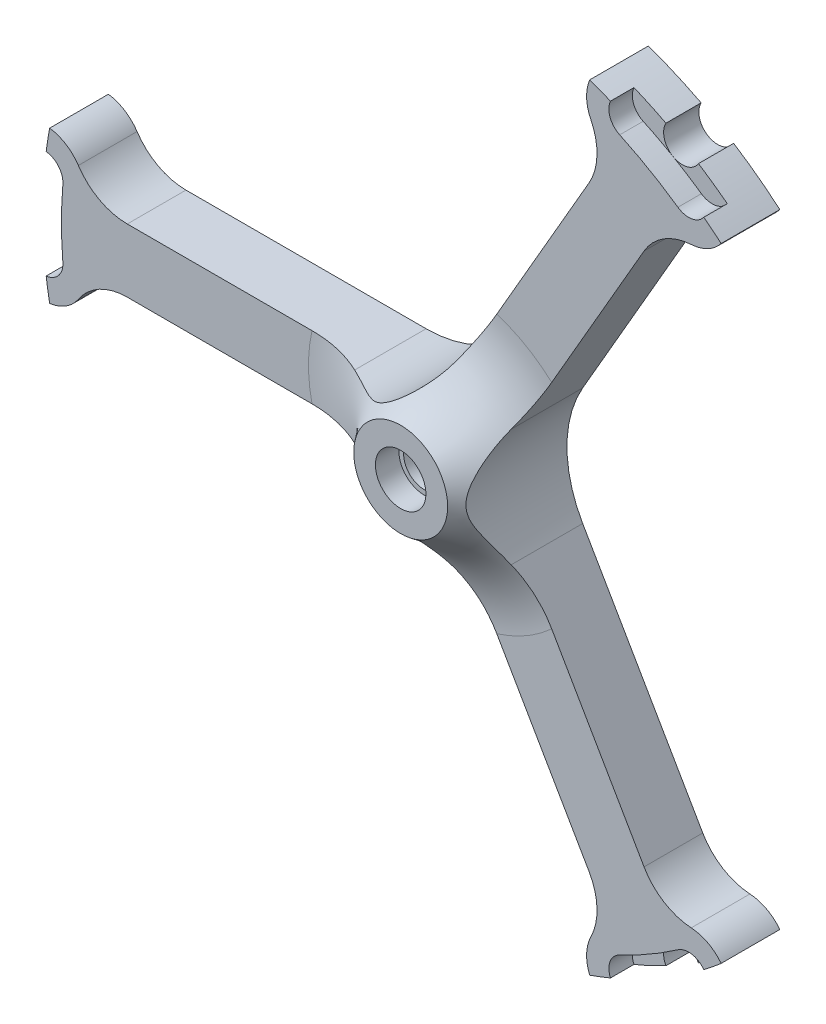
SolidWorks part; units mm, degrees
ref_plane "Plan de face" through (0, 0, 0) normal (0, 0, 1) x (1, 0, 0)
ref_plane "Plan de dessus" through (0, 0, 0) normal (0, 1, 0) x (1, 0, 0)
ref_plane "Plan de droite" through (0, 0, 0) normal (1, 0, 0) x (0, 0, -1)
sketch "Esquisse1" plane through (0, 0, 0) normal (0, 0, 1) x (1, 0, 0)
  line L19 (-1000, 0) -> (49000, 0) construction
  line L21 (-27.7888, 2.7) -> (-7.3323, 2.7)
  line L23 (-27.7888, -2.7) -> (-7.3323, -2.7)
  line L33 (16.2327, 22.7158) -> (6.0044, 5)
  line L34 (11.5561, 25.4158) -> (1.3279, 7.7)
  line L35 (11.5561, -25.4158) -> (1.3279, -7.7)
  line L36 (16.2327, -22.7158) -> (6.0044, -5)
  arc A0 (-34.3972, 6.4678) -> (-34.6976, 4.5906) centre (0, 0) ccw
  arc A7 (-33.2771, 2.8629) -> (-34.6976, 4.5906) centre (-34.8712, 3) ccw
  arc A8 (-33.2771, -2.8629) -> (-34.6976, -4.5906) centre (-34.8712, -3) cw
  arc A12 (-33.2771, 2.8629) -> (-33.2771, -2.8629) centre (0, 0) ccw
  arc A13 (-31.9549, 4.9353) -> (-34.3972, 6.4678) centre (-34.8712, 3) ccw
  arc A14 (-31.9549, -4.9353) -> (-34.3972, -6.4678) centre (-34.8712, -3) cw
  arc A15 (-34.6976, -4.5906) -> (-34.3972, -6.4678) centre (0, 0) ccw
  arc A16 (-27.7888, -2.7) -> (-31.9549, -4.9353) centre (-27.7888, -7.7) ccw
  arc A17 (-27.7888, 2.7) -> (-31.9549, 4.9353) centre (-27.7888, 7.7) cw
  arc A48 (22.7998, 26.555) -> (21.3244, 27.7538) centre (0, 0) ccw
  arc A49 (19.1178, 27.3874) -> (21.3244, 27.7538) centre (20.0337, 28.6993) ccw
  arc A50 (14.1592, 30.2502) -> (13.3733, 32.3443) centre (14.8375, 31.6993) cw
  arc A51 (19.1178, 27.3874) -> (14.1592, 30.2502) centre (0, 0) ccw
  arc A52 (20.2516, 25.2061) -> (22.7998, 26.555) centre (20.0337, 28.6993) ccw
  arc A53 (11.7034, 30.1414) -> (11.5974, 33.0227) centre (14.8375, 31.6993) cw
  arc A54 (13.3733, 32.3443) -> (11.5974, 33.0227) centre (0, 0) ccw
  arc A55 (11.5561, 25.4158) -> (11.7034, 30.1414) centre (7.226, 27.9158) ccw
  arc A56 (16.2327, 22.7158) -> (20.2516, 25.2061) centre (20.5628, 20.2158) cw
  arc A57 (11.5974, -33.0227) -> (13.3733, -32.3443) centre (0, 0) ccw
  arc A58 (14.1592, -30.2502) -> (13.3733, -32.3443) centre (14.8375, -31.6993) ccw
  arc A59 (19.1178, -27.3874) -> (21.3244, -27.7538) centre (20.0337, -28.6993) cw
  arc A60 (14.1592, -30.2502) -> (19.1178, -27.3874) centre (0, 0) ccw
  arc A61 (11.7034, -30.1414) -> (11.5974, -33.0227) centre (14.8375, -31.6993) ccw
  arc A62 (20.2516, -25.2061) -> (22.7998, -26.555) centre (20.0337, -28.6993) cw
  arc A63 (21.3244, -27.7538) -> (22.7998, -26.555) centre (0, 0) ccw
  arc A64 (16.2327, -22.7158) -> (20.2516, -25.2061) centre (20.5628, -20.2158) ccw
  arc A65 (11.5561, -25.4158) -> (11.7034, -30.1414) centre (7.226, -27.9158) cw
  arc A66 (-7.3323, -2.7) -> (1.3279, -7.7) centre (-7.3323, -12.7) cw
  arc A67 (6.0044, -5) -> (6.0044, 5) centre (14.6647, 0) cw
  arc A68 (1.3279, 7.7) -> (-7.3323, 2.7) centre (-7.3323, 12.7) cw
  point P38 (0, 0)
  point P50 (3.1177, 0)
  point P55 (0, 0)
  point P56 (0, 0)
  point P80 (0, 0)
  dimension "D1" = 70
  dimension "D3" = 3
  dimension "D2" = 3.2
  dimension "D4" = 5
  dimension "D5" = 10
extrude "Boss.-Extru.1" add sketch "Esquisse1" along normal blind 5
sketch "Esquisse7" plane through (0, 0, 0) normal (0, 0, -1) x (-1, 0, 0)
  line L0 (-1000, 0) -> (49000, 0) construction
  arc A0 (34.6976, -4.5906) -> (34.6976, 4.5906) centre (0, 0) ccw
  arc A2 (33.2771, -2.8629) -> (33.2771, 2.8629) centre (0, 0) ccw
  arc A4 (34.9634, 1.5996) -> (34.9634, -1.5996) centre (35, 0) ccw
  arc A5 (34.6976, 4.5906) -> (33.2771, 2.8629) centre (34.8712, 3) ccw
  arc A6 (33.2771, -2.8629) -> (33.2771, 2.8629) centre (0, 0) ccw construction
  arc A7 (34.6976, -4.5906) -> (33.2771, -2.8629) centre (34.8712, -3) cw
  arc A8 (-21.3244, -27.7538) -> (-13.3733, -32.3443) centre (0, 0) ccw
  arc A9 (-19.1178, -27.3874) -> (-14.1592, -30.2502) centre (0, 0) ccw
  arc A10 (-16.0964, -31.079) -> (-18.867, -29.4794) centre (-17.5, -30.3109) ccw
  arc A11 (-13.3733, -32.3443) -> (-14.1592, -30.2502) centre (-14.8375, -31.6993) ccw
  arc A12 (-21.3244, -27.7538) -> (-19.1178, -27.3874) centre (-20.0337, -28.6993) cw
  arc A13 (-13.3733, 32.3443) -> (-21.3244, 27.7538) centre (0, 0) ccw
  arc A14 (-14.1592, 30.2502) -> (-19.1178, 27.3874) centre (0, 0) ccw
  arc A15 (-18.867, 29.4794) -> (-16.0964, 31.079) centre (-17.5, 30.3109) ccw
  arc A16 (-21.3244, 27.7538) -> (-19.1178, 27.3874) centre (-20.0337, 28.6993) ccw
  arc A17 (-13.3733, 32.3443) -> (-14.1592, 30.2502) centre (-14.8375, 31.6993) cw
  point P36 (0, 0)
  arc M44 (34.6976, -4.5906) -> (33.2771, -2.8629) centre (34.8712, -3) cw
  arc M45 (33.2771, -2.8629) -> (33.2771, 2.8629) centre (0, 0) ccw
  arc M46 (33.2771, 2.8629) -> (34.6976, 4.5906) centre (34.8712, 3) cw
  arc M56 (-13.3733, 32.3443) -> (-14.1592, 30.2502) centre (-14.8375, 31.6993) cw
  arc M57 (-14.1592, 30.2502) -> (-19.1178, 27.3874) centre (0, 0) ccw
  arc M58 (-19.1178, 27.3874) -> (-21.3244, 27.7538) centre (-20.0337, 28.6993) cw
  arc M68 (-21.3244, -27.7538) -> (-19.1178, -27.3874) centre (-20.0337, -28.6993) cw
  arc M69 (-19.1178, -27.3874) -> (-14.1592, -30.2502) centre (0, 0) ccw
  arc M70 (-14.1592, -30.2502) -> (-13.3733, -32.3443) centre (-14.8375, -31.6993) cw
  dimension "D1" = 3.2
  dimension "D3" = 3.2
  dimension "D4" = 70
  dimension "D2" = 3
extrude "Boss.-Extru.5" add sketch "Esquisse7" against normal blind 3 contours A4 A0 A2 M46 | A4 A0 M45 M44 | A10 A8 A9 M70 | A10 A8 M69 M68 | A15 A13 M57 M56 | A15 A13 A14 M58 region at (-34.0862, -2.7129, 0) region at (-34.0862, 2.7129, 0) region at (19.3926, -28.1631, 0) region at (14.6937, -30.876, 0) region at (14.6937, 30.876, 0) region at (19.3926, 28.1631, 0)
sketch "Esquisse4" plane through (0, 0, 5) normal (0, 0, 1) x (1, 0, 0)
  circle A1 centre (0, 0) radius 4
  dimension "D1" = 8
extrude "Boss.-Extru.3" add sketch "Esquisse4" along normal blind 4.5
sketch "Esquisse5" plane through (0, 0, 9.5) normal (0, 0, 1) x (1, 0, 0)
  circle A0 centre (0, 0) radius 2.15
  dimension "D1" = 4.3
extrude "Enlèv. mat.-Extru.2" cut sketch "Esquisse5" against normal blind 2
fillet "Congé1" radius 10 1 edges at (4, 0, 5)
sketch "Esquisse6" plane through (0, 0, 7.5) normal (0, 0, 1) x (1, 0, 0)
  circle A0 centre (0, 0) radius 1.75
  dimension "D1" = 3.5
extrude "Enlèv. mat.-Extru.3" cut sketch "Esquisse6" against normal up to next
